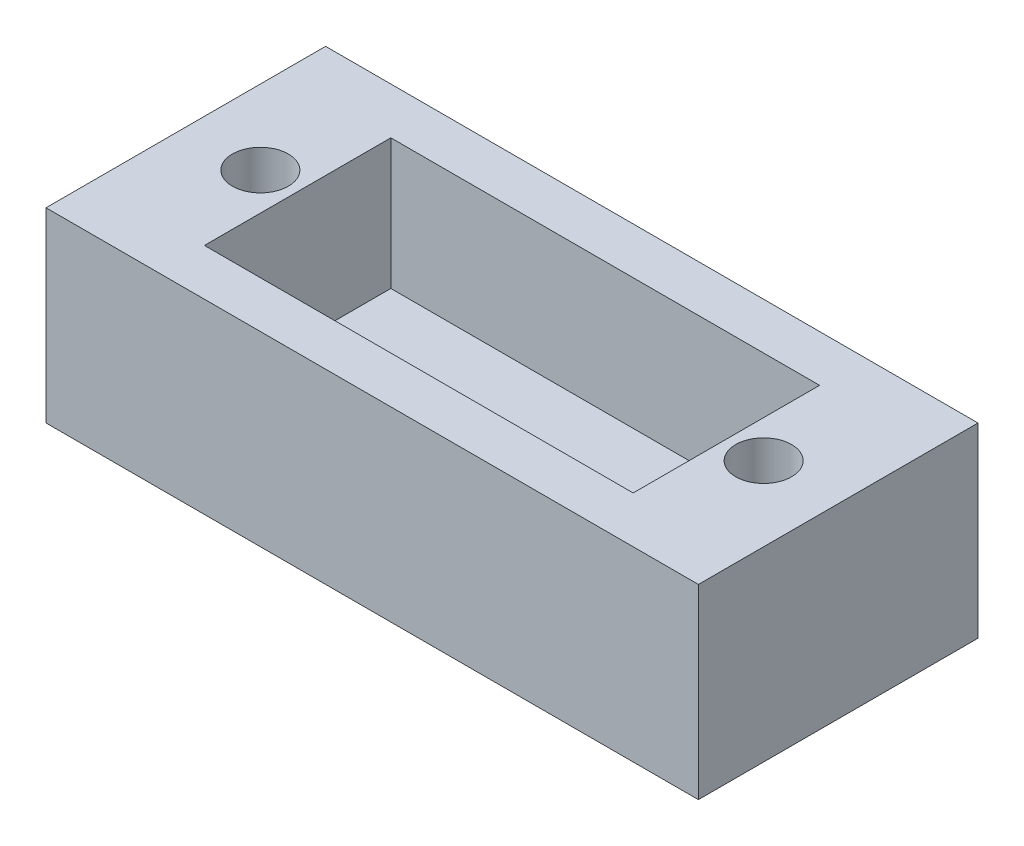
SolidWorks part; units mm, degrees
ref_plane "Спереди" through (0, 0, 0) normal (0, 0, 1) x (1, 0, 0)
ref_plane "Сверху" through (0, 0, 0) normal (0, 1, 0) x (1, 0, 0)
ref_plane "Справа" through (0, 0, 0) normal (1, 0, 0) x (0, 0, -1)
sketch "Эскиз1" plane through (0, 0, 0) normal (0, 1, 0) x (1, 0, 0)
  line L0 (0, 0) -> (21.8716, 0) construction
  line L1 (-10, -2) -> (10, -2)
  line L2 (-10, -2) -> (-10, 2)
  line L3 (-10, 2) -> (10, 2)
  line L4 (10, -2) -> (10, 2)
  line L5 (-10, -2) -> (10, 2) construction
  line L6 (-10, 2) -> (10, -2) construction
  line L8 (-17.5, -7.5) -> (17.5, -7.5)
  line L9 (-17.5, -7.5) -> (-17.5, 7.5)
  line L10 (-17.5, 7.5) -> (17.5, 7.5)
  line L11 (17.5, -7.5) -> (17.5, 7.5)
  line L12 (-17.5, -7.5) -> (17.5, 7.5) construction
  line L13 (-17.5, 7.5) -> (17.5, -7.5) construction
  line L14 (-11.5, -5) -> (11.5, -5)
  line L15 (-11.5, -5) -> (-11.5, 5)
  line L16 (-11.5, 5) -> (11.5, 5)
  line L17 (11.5, -5) -> (11.5, 5)
  line L18 (-11.5, -5) -> (11.5, 5) construction
  line L19 (-11.5, 5) -> (11.5, -5) construction
  circle A0 centre (13.5, 0) radius 1.5
  circle A1 centre (-13.5, 0) radius 1.5
  point P0 (0, 0)
  point P12 (0, 0)
  point P19 (0, 0)
  dimension "D3" = 3
  dimension "D1" = 20
  dimension "D2" = 4
  dimension "D4" = 13.5
  dimension "D5" = 13.5
  dimension "D6" = 15
  dimension "D7" = 35
  dimension "D8" = 10
  dimension "D9" = 23
extrude "Бобышка-Вытянуть1" add sketch "Эскиз1" along normal blind 10 contours L8 L11 L10 L9 A1 A0 L17 L14 L15 L16 region at (-17.1192, 0, 0)
extrude "Бобышка-Вытянуть2" add sketch "Эскиз1<3>" along normal blind 3 contours L14 L17 L16 L15 L4 L1 L2 L3 region at (-11.2492, 0, 0)
sketch "Эскиз1<3>" plane through (0, 0, 0) normal (0, 1, 0) x (1, 0, 0) same geometry as "Эскиз1"
